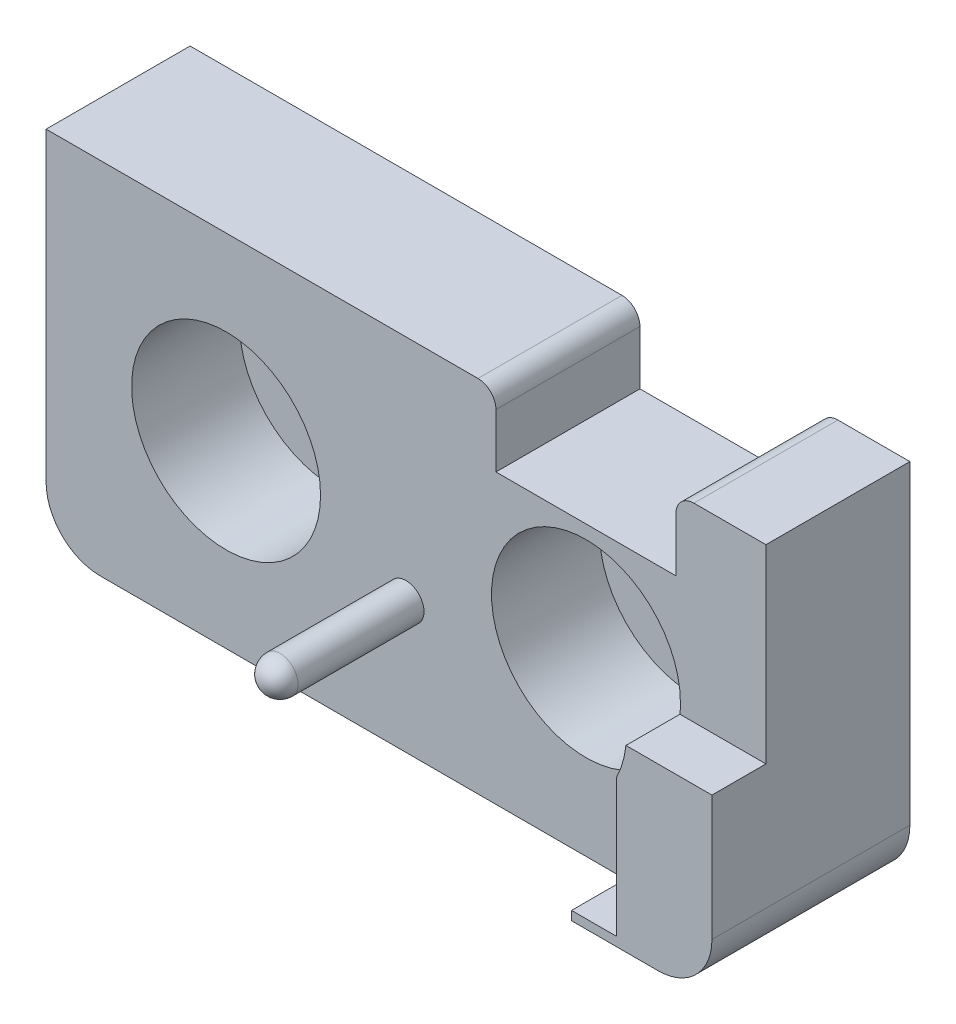
SolidWorks part; units mm, degrees
ref_plane "Front Plane" through (0, 0, 0) normal (0, 0, 1) x (1, 0, 0)
ref_plane "Top Plane" through (0, 0, 0) normal (0, 1, 0) x (1, 0, 0)
ref_plane "Right Plane" through (0, 0, 0) normal (1, 0, 0) x (0, 0, -1)
sketch "Sketch1" plane through (0, 0, 0) normal (0, 0, 1) x (1, 0, 0)
  line L0 (10, 10) -> (10, 6) construction
  line L1 (-17, -10) -> (17, -10)
  line L2 (-20, -7) -> (-20, 10)
  line L3 (-20, 10) -> (4, 10)
  line L4 (20, -7) -> (20, 10)
  line L5 (-20, -10) -> (20, 10) construction
  line L6 (-20, 10) -> (20, -10) construction
  line L8 (5, 9) -> (5, 6)
  line L9 (5, 6) -> (15, 6)
  line L10 (15, 9) -> (15, 6)
  line L11 (-10, 10) -> (-10, -10) construction
  line L12 (10, 6) -> (10, -10) construction
  line L13 (16, 10) -> (20, 10)
  arc A0 (16, 10) -> (15, 9) centre (16, 9) ccw
  arc A1 (4, 10) -> (5, 9) centre (4, 9) cw
  arc A2 (17, -10) -> (20, -7) centre (17, -7) ccw
  arc A3 (-17, -10) -> (-20, -7) centre (-17, -7) cw
  point P0 (0, 0)
  dimension "D7" = 1
  dimension "D8" = 3
  dimension "D1" = 40
  dimension "D2" = 20
  dimension "D3" = 10
  dimension "D4" = 4
  dimension "D5" = 10
  dimension "D6" = 10
extrude "Boss-Extrude1" add sketch "Sketch1" along normal blind 8
hole_wizard "CBORE for M5 SHCS1" positions "Sketch3" profile "Sketch2" counterbore size "M5" standard "ANSI Metric" end condition up to next
sketch "Sketch3" plane through (0, 0, 8) normal (0, 0, 1) x (1, 0, 0)
  line L0 (-10, 10) -> (-10, -10) construction
  line L3 (10, 6) -> (10, -10) construction
  line L4 (-13.9419, 10) -> (-13.9419, -10) construction
  line L5 (-20, 10) -> (4, 10) construction
  line L6 (-17, -10) -> (17, -10) construction
  point P0 (-10, 0)
  point P2 (10, 0)
  point P24 (-13.9419, 0)
sketch "Sketch2" plane through (-10, 0, 8) normal (1, 0, 0) x (0, -1, 0)
  line L0 (0, 0) -> (0, 8)
  line L1 (0, 8) -> (2.75, 8)
  line L3 (2.75, 8) -> (2.75, 6)
  line L4 (2.75, 6) -> (5.25, 6)
  line L5 (5.25, 6) -> (5.25, 0)
  line L7 (5.25, 0) -> (0, 0)
  line L11 (0, -6.35) -> (0, 107.95) construction
  dimension "Thru Hole Dia." = 5.5
  dimension "Thru Hole Depth" = 8
  dimension "C'Bore Dia." = 10.5
  dimension "C'Bore Depth" = 6
sketch "Sketch6" plane through (0, 0, 8) normal (0, 0, 1) x (1, 0, 0)
  line L0 (-20, -2.7273) -> (20, -2.7273) construction
  line L1 (-20, -7) -> (-20, 10) construction
  line L2 (20, -7) -> (20, 10) construction
  line L3 (11.5, -2.7273) -> (-2, -2.7273) construction
  line L4 (0, -10) -> (0, -2.7273) construction
  line L5 (-17, -10) -> (17, -10) construction
  circle A0 centre (0, -2.7273) radius 1
  dimension "D1" = 2
extrude "Boss-Extrude3" add sketch "Sketch6" along normal blind 8
fillet "Fillet2" radius 1 1 edges at (1, -2.7273, 16)
sketch "Sketch7" plane through (0, 0, 8) normal (0, 0, 1) x (1, 0, 0)
  line L0 (20, -7) -> (20, 10) construction
  line L1 (20, -0.55) -> (15.2211, -0.55)
  line L2 (20, -0.55) -> (20, -7.5)
  line L3 (14.5, -1.05) -> (14.5, -9.75) construction
  line L7 (11.5, -0.55) -> (14, -0.55) construction
  line L8 (14.7, -2.3393) -> (14.7, -10)
  line L11 (-17, -10) -> (17, -10) construction
  line L12 (14.7, -10) -> (12.2, -10)
  line L13 (12.2, -10) -> (12.2, -10.5)
  line L14 (12.2, -10.5) -> (17, -10.5)
  arc A0 (20, -7.5) -> (17, -10.5) centre (17, -7.5) cw
  circle A1 centre (10, 0) radius 5.25 construction
  arc A2 (14.7, -2.3393) -> (15.2211, -0.55) centre (10, 0) ccw
  point P6 (14.7, -10)
  dimension "D2" = 0.5
  dimension "D4" = 3
  dimension "D1" = 0.2
  dimension "D3" = 2.5
  dimension "D5" = 5.3
extrude "Boss-Extrude4" add sketch "Sketch7" along normal blind 3 and the other way up to surface other way up to face at (-7.25, 0, 0)
